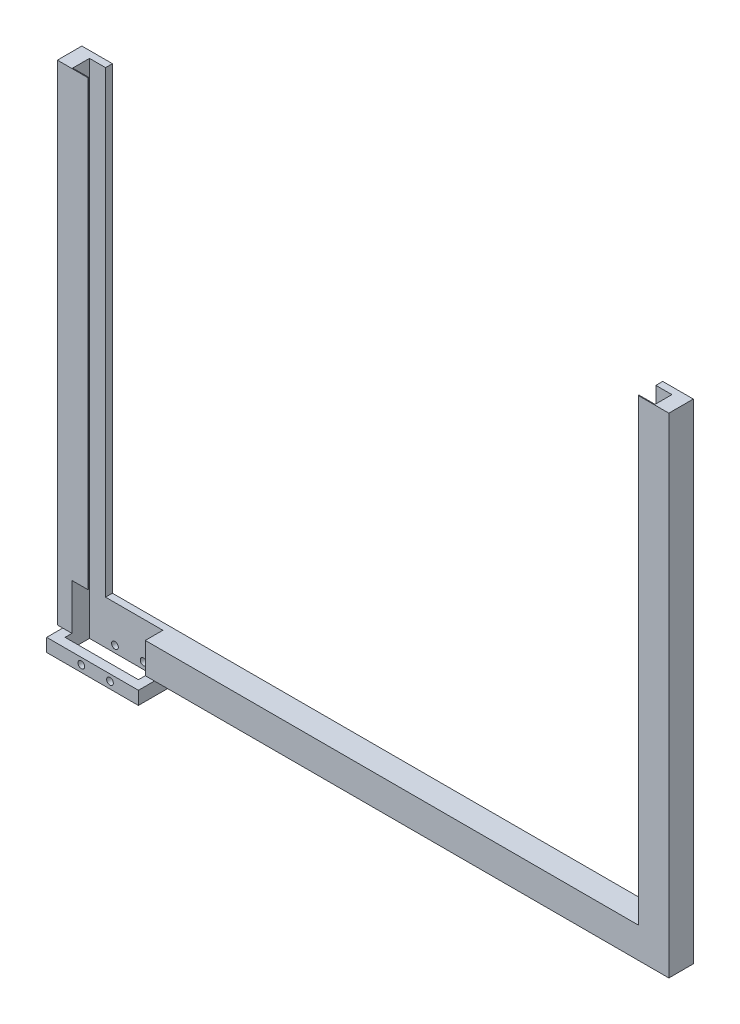
SolidWorks part; units mm, degrees
ref_plane "Front Plane" through (0, 0, 0) normal (0, 0, 1) x (1, 0, 0)
ref_plane "Top Plane" through (0, 0, 0) normal (0, 1, 0) x (1, 0, 0)
ref_plane "Right Plane" through (0, 0, 0) normal (1, 0, 0) x (0, 0, -1)
sketch "Croquis1" plane through (0, 0, 0) normal (0, 1, 0) x (1, 0, 0)
  line L1 (-100, -85) -> (100, -85)
  line L2 (-100, -85) -> (-100, 85)
  line L3 (-100, 85) -> (100, 85)
  line L4 (100, -85) -> (100, 85)
  line L5 (-100, -85) -> (100, 85) construction
  line L6 (-100, 85) -> (100, -85) construction
  point P0 (0, 0)
  dimension "D1" = 200
  dimension "D2" = 170
extrude "Saliente-Extruir1" add sketch "Croquis1" along normal blind 10
sketch "Croquis2" plane through (0, 10, 0) normal (0, 1, 0) x (1, 0, 0)
  line L0 (-100, 85) -> (-100, -85) construction
  line L1 (-100, -85) -> (-90, -85)
  line L2 (-100, -85) -> (-100, 85)
  line L3 (-100, 85) -> (-90, 85)
  line L4 (-90, -85) -> (-90, 85)
  line L5 (-100, -85) -> (-90, 85) construction
  line L6 (-100, 85) -> (-90, -85) construction
  line L7 (0, 0) -> (0, 38.7105) construction
  line L8 (100, 85) -> (90, -85) construction
  line L9 (100, -85) -> (90, 85) construction
  line L10 (90, -85) -> (90, 85)
  line L11 (100, 85) -> (90, 85)
  line L12 (100, -85) -> (100, 85)
  line L13 (100, -85) -> (90, -85)
  line L14 (-90, 85) -> (90, 85)
  line L15 (-90, 75) -> (90, 75)
  line L16 (-90, -75) -> (-30.21, -75)
  line L17 (-30.21, -75) -> (-30.21, -85)
  line L18 (-100, -85) -> (100, -85) construction
  line L19 (-30.21, -85) -> (-90, -85)
  line L20 (59.79, -85) -> (59.79, -75)
  line L21 (59.79, -75) -> (90, -75)
  line L22 (59.79, -85) -> (90, -85)
  point P0 (-95, 0)
  point P14 (95, 0)
  line M14 (100, -85) -> (100, 85)
  line M15 (100, 85) -> (-100, 85)
  line M16 (-100, 85) -> (-100, -85)
  line M17 (-100, -85) -> (100, -85)
  dimension "D1" = 10
  dimension "D2" = 10
  dimension "D3" = 10
  dimension "D4" = 69.79
  dimension "D5" = 40.21
  dimension "D6" = 10
extrude "Saliente-Extruir2" add sketch "Croquis2" along normal blind 150 contours L4 M17 M15 M16 | L10 M17 M14 M15 | L17 L16 L4 M17 | L21 L20 L10 M17 region at (-95, 10, 0) region at (-60.105, 10, 80) region at (74.895, 10, 80) region at (95, 10, 0)
sketch "Croquis3" plane through (0, 160, 0) normal (0, 1, 0) x (1, 0, 0)
  line L0 (-30.21, -75) -> (59.79, -75)
  line L1 (59.79, -75) -> (59.79, -85)
  line L2 (59.79, -85) -> (-30.21, -85)
  line L3 (-30.21, -85) -> (-30.21, -75)
extrude "Saliente-Extruir3" add sketch "Croquis3" against normal blind 100
sketch "Croquis4" plane through (0, 10, 65) normal (0, 1, 0) x (-1, 0, 0)
  line L1 (95.25, -147.75) -> (84.75, -147.75)
  line L2 (95.25, -147.75) -> (95.25, -142.25)
  line L3 (95.25, -142.25) -> (84.75, -142.25)
  line L4 (84.75, -147.75) -> (84.75, -142.25)
  line L5 (95.25, -147.75) -> (84.75, -142.25) construction
  line L6 (95.25, -142.25) -> (84.75, -147.75) construction
  line L8 (90, -142.25) -> (90, -147.75)
  line L9 (0, -65) -> (0, 148.7254) construction
  line L10 (-95.25, -142.25) -> (-84.75, -147.75) construction
  line L11 (-95.25, -147.75) -> (-84.75, -142.25) construction
  line L12 (-90, -142.25) -> (-90, -147.75)
  line L13 (-84.75, -147.75) -> (-84.75, -142.25)
  line L14 (-95.25, -142.25) -> (-84.75, -142.25)
  line L15 (-95.25, -147.75) -> (-95.25, -142.25)
  line L16 (-95.25, -147.75) -> (-84.75, -147.75)
  line L17 (-90, -150) -> (90, -150) construction
  line L18 (90, 10) -> (90, -150) construction
  point P0 (90, -145)
  point P20 (-90, -145)
  dimension "D1" = 5.5
  dimension "D2" = 5
  dimension "D3" = 10.5
extrude "Cortar-Extruir1" cut sketch "Croquis4" along normal blind 170 contours L2 L3 L1 | L15 L16 L14 region at (-92.625, 10, -80) region at (92.625, 10, -80)
sketch "Croquis7" plane through (0, 0, 85) normal (0, 0, 1) x (1, 0, 0)
  line L0 (-30.21, 60) -> (-30.21, 70)
  line L1 (-30.21, 70) -> (59.79, 70)
  line L2 (59.79, 70) -> (59.79, 60)
  line L3 (-30.21, 60) -> (59.79, 60)
  dimension "D1" = 10
extrude "Saliente-Extruir4" add sketch "Croquis7" along normal blind 5
sketch "Croquis8" plane through (0, 160, 0) normal (0, 1, 0) x (1, 0, 0)
  line L4 (98, 70) -> (98, -83)
  line L5 (98, -83) -> (-98, -83)
  line L6 (-98, -83) -> (-98, 70)
  line L8 (-98, 70) -> (-92, 70)
  line L9 (-92, 70) -> (-92, -77)
  line L10 (-92, -77) -> (92, -77)
  line L11 (92, -77) -> (92, 70)
  line L12 (92, 70) -> (98, 70)
  line L13 (100, -85) -> (100, 85) construction
  line L14 (90, -75) -> (90, 77.25) construction
  line L25 (-100, -85) -> (100, -85) construction
  line L26 (-90, -75) -> (90, -75) construction
  line L33 (-90, -75) -> (-90, 77.25) construction
  line L34 (-100, 85) -> (-100, -85) construction
  line L68 (-90, 85) -> (-100, 85) construction
  line L69 (100, 85) -> (90, 85) construction
  dimension "D1" = 2
  dimension "D2" = 2
  dimension "D3" = 2
  dimension "D4" = 2
  dimension "D5" = 2
  dimension "D7" = 15
  dimension "D8" = 15
  dimension "D6" = 2
extrude "Cortar-Extruir3" cut sketch "Croquis8" against normal blind 10 contours L8 region at (95.5135, 160, 6.5)
sketch "Croquis9" plane through (0, 10, 0) normal (0, 1, 0) x (1, 0, 0)
  line L0 (-95.25, 77.25) -> (-95.25, 82.75)
  line L1 (-95.25, 82.75) -> (-71.25, 82.75)
  line L2 (-71.25, 82.75) -> (-71.25, 77.25)
  line L4 (-71.25, 77.25) -> (-71.25, 74.75)
  line L5 (-71.25, 74.75) -> (-95.25, 74.75)
  line L6 (-95.25, 74.75) -> (-95.25, 77.25)
  dimension "D1" = 24
  dimension "D2" = 2.5
  dimension "D3" = 2.5
extrude "Cortar-Extruir4" cut sketch "Croquis9" against normal blind 30
extrude "Cortar-Extruir5" cut sketch "Croquis9<2>" along normal blind 5
sketch "Croquis9<2>" plane through (0, 10, 0) normal (0, 1, 0) x (1, 0, 0) same geometry as "Croquis9"
sketch "Croquis10" plane through (0, 0, 0) normal (0, -1, 0) x (1, 0, 0)
  line L0 (-71.25, -82.75) -> (-95.25, -82.75)
  line L1 (-95.25, -82.75) -> (-95.25, -74.75)
  line L2 (-95.25, -74.75) -> (-71.25, -74.75)
  line L3 (-71.25, -74.75) -> (-71.25, -82.75)
  line L4 (-68.25, -85.25) -> (-98.25, -85.25)
  line L5 (-98.25, -85.25) -> (-98.25, -71.75)
  line L6 (-98.25, -71.75) -> (-68.25, -71.75)
  line L7 (-68.25, -71.75) -> (-68.25, -85.25)
  dimension "D1" = 3
  dimension "D2" = 3
  dimension "D3" = 3
  dimension "D4" = 2.5
extrude "Saliente-Extruir5" add sketch "Croquis10" along normal blind 4.3
sketch "Croquis11" plane through (0, 0, -71.75) normal (0, 0, 1) x (1, 0, 0)
  line L0 (-68.25, -4.3) -> (-68.25, 0) construction
  line L1 (-68.25, 0) -> (-98.25, 0) construction
  circle A0 centre (-77.55, -2.1) radius 1.1
  circle A1 centre (-86.93, -2.1) radius 1.1
  dimension "D1" = 2.2
  dimension "D2" = 2.2
  dimension "D3" = 9.3
  dimension "D4" = 9.38
  dimension "D5" = 2.1
  dimension "D6" = 2.1
extrude "Cortar-Extruir6" cut sketch "Croquis11" against normal blind 14.3
sketch "Croquis12" plane through (0, 0, 0) normal (0, -1, 0) x (1, 0, 0)
  line L0 (-100, -85) -> (-100, 85) construction
  line L1 (0, 0) -> (-59.6706, 0) construction
  line L2 (100, -85) -> (-68.25, -85) construction
  circle A0 centre (-91.5, -55) radius 1.75
  circle A1 centre (18.5, -55) radius 1.75
  circle A2 centre (-91.5, 55) radius 1.75
  circle A3 centre (18.5, 55) radius 1.75
  dimension "D1" = 3.5
  dimension "D4" = 3.5
  dimension "D5" = 30
  dimension "D6" = 30
  dimension "D2" = 8.5
  dimension "D3" = 118.5
extrude "Cortar-Extruir7" cut sketch "Croquis12" against normal blind 6.4
sketch "Croquis13" plane through (0, 0, 85) normal (0, 0, 1) x (1, 0, 0)
  line L1 (-30.21, 10) -> (59.79, 10) construction
  line L2 (-30.21, 60) -> (-30.21, 10) construction
  line L3 (14.79, 10) -> (14.79, 41.54) construction
  circle A0 centre (-50.21, 24) radius 1.7
  circle A1 centre (79.79, 24) radius 1.7
  dimension "D3" = 3.4
  dimension "D1" = 14
  dimension "D2" = 20
extrude "Cortar-Extruir8" cut sketch "Croquis13" against normal blind 5
sketch "Croquis14" plane through (0, 0, 90) normal (0, 0, 1) x (1, 0, 0)
  line L0 (-30.21, 70) -> (-30.21, 60)
  line L1 (-30.21, 60) -> (-29.91, 60)
  line L2 (-30.21, 60) -> (59.79, 60) construction
  line L3 (-29.91, 60) -> (-29.91, 70)
  line L4 (59.79, 70) -> (-30.21, 70) construction
  line L5 (-29.91, 70) -> (-30.21, 70)
  line L6 (59.79, 70) -> (59.49, 70)
  line L7 (59.49, 70) -> (59.49, 60)
  line L8 (59.49, 60) -> (59.79, 60)
  line L9 (59.79, 60) -> (59.79, 70) construction
  line L10 (59.79, 60) -> (59.79, 70)
  dimension "D1" = 0.3
  dimension "D2" = 0.3
extrude "Cortar-Extruir9" cut sketch "Croquis14" against normal blind 5
sketch "Croquis15" plane through (0, 0, 85) normal (0, 0, 1) x (1, 0, 0)
  line L0 (14.79, 0) -> (94.79, 0)
  line L1 (-100, 0) -> (100, 0) construction
  line L2 (94.79, 0) -> (94.79, 4.8)
  line L3 (94.79, 4.8) -> (14.79, 4.8)
  line L4 (14.79, 4.8) -> (-65.21, 4.8)
  line L5 (-65.21, 4.8) -> (-65.21, 0)
  line L6 (-65.21, 0) -> (14.79, 0)
  line L7 (-30.21, 10) -> (59.79, 10) construction
  point P10 (14.79, 10)
  dimension "D1" = 80
  dimension "D2" = 4.8
  dimension "D3" = 80
extrude "Saliente-Extruir6" add sketch "Croquis15" along normal blind 5
sketch "Croquis16" plane through (0, 0, 85) normal (0, 0, 1) x (1, 0, 0)
  line L0 (-100, 0) -> (-100, 160)
  line L1 (-100, 160) -> (100, 160)
  line L2 (100, 160) -> (100, 0)
  line L3 (100, 0) -> (-100, 0)
extrude "Cortar-Extruir10" cut sketch "Croquis16" against normal blind 162
extrude "Cortar-Extruir11" cut sketch "Croquis16<2>" along normal blind 162
sketch "Croquis16<2>" plane through (0, 0, 85) normal (0, 0, 1) x (1, 0, 0) same geometry as "Croquis16"
